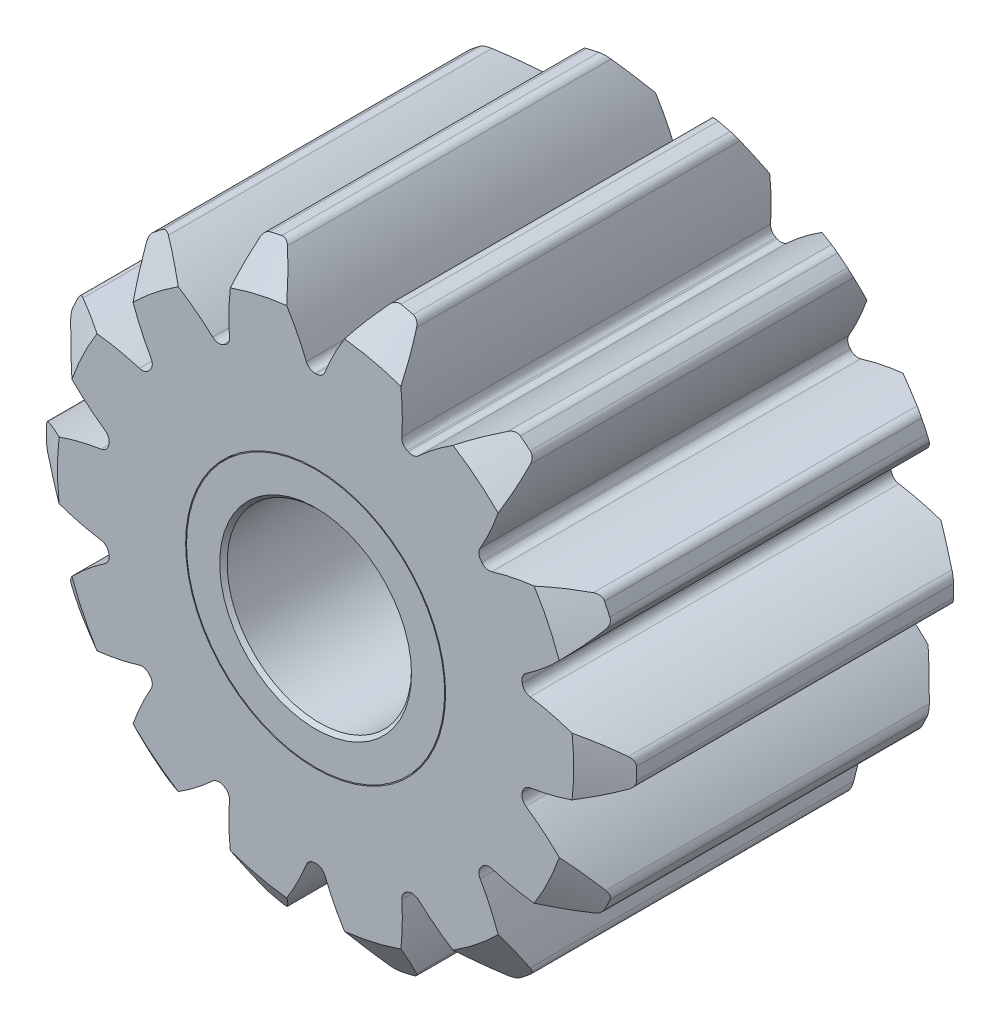
SolidWorks part; units mm, degrees
ref_plane "前视基准面" through (0, 0, 0) normal (0, 0, 1) x (1, 0, 0)
ref_plane "上视基准面" through (0, 0, 0) normal (0, 1, 0) x (1, 0, 0)
ref_plane "右视基准面" through (0, 0, 0) normal (1, 0, 0) x (0, 0, -1)
sketch "草图1" plane through (0, 0, 0) normal (1, 0, 0) x (0, 0, -1)
  line L0 (0, 0) -> (20, 0) construction
  line L1 (0, 5) -> (20, 5)
  line L4 (20, 5) -> (20, 16)
  line L5 (20, 16) -> (0, 16)
  line L6 (0, 16) -> (0, 5)
  line L7 (0, 0) -> (-2, 0) construction
  line L8 (-2, 0) -> (-2, -14) construction
  dimension "P" = 10
  dimension "B" = 20
  dimension "M" = 2
  dimension "Z" = 14
  dimension "D" = 32
sketch "草图2" plane through (0, 0, 0) normal (0, 0, 1) x (1, 0, 0)
  line L0 (0, 5) -> (0, 9) construction
  circle A0 centre (0, 0) radius 5
  circle A3 centre (0, 0) radius 7
  point P6 (0, 7)
  dimension "(D1)" = 4
sketch "草图11" plane through (-11.8785, -4, 0) normal (0, 0, 1) x (1, 0, 0)
  line L0 (11.8785, 4) -> (27.8785, 4) construction
  line L1 (25.7905, 2.4325) -> (11.8785, 4) construction
  circle A0 centre (11.8785, 4) radius 11.5
  arc A1 (23.1689, 1.8143) -> (23.3785, 4) centre (11.8785, 4) ccw construction
  arc A2 (25.7905, 2.4325) -> (25.8785, 4) centre (11.8785, 4) ccw construction
  arc A3 (27.8662, 3.3718) -> (27.8662, 4.6282) centre (11.8785, 4) ccw construction
  arc A4 (23.1689, 1.8143) -> (27.8662, 3.3718) centre (21.5405, 14.5867) ccw construction
  point P1 (25.8785, 4)
  point P7 (11.8785, 6)
  point P13 (25.7905, 2.4325)
  point P17 (27.8662, 4.6282)
  point P18 (23.1689, 6.1857)
  dimension "D1" = 32
  dimension "D" = 28
  dimension "D2" = 23
  dimension "m" = 2
  dimension "z" = 14
  dimension "D3" = 6.429
  dimension "D4" = 1.2566
  dimension "D5" = 4.3982
extrude "拉伸-齿轮a" add sketch "草图11" against normal blind 20
sketch "草图3" plane through (-1.3611, -4, 0) normal (0, 0, 1) x (1, 0, 0)
  line L1 (1.3611, 4) -> (17.3611, 4) construction
  line L2 (12.8611, 4) -> (17.3611, 4) construction
  circle A2 centre (1.3611, 4) radius 11.5 construction
  arc A3 (12.6514, 1.8143) -> (17.3487, 3.3718) centre (11.0231, 14.5867) ccw construction
  arc A4 (17.3487, 3.3718) -> (17.3487, 4.6282) centre (1.3611, 4) ccw construction
  arc A5 (12.6514, 1.8143) -> (12.6514, 6.1857) centre (1.3611, 4) ccw
  arc A6 (12.6514, 1.8143) -> (17.3487, 3.3718) centre (11.0231, 14.5867) ccw
  arc A7 (17.3487, 3.3718) -> (17.3487, 4.6282) centre (1.3611, 4) ccw
  arc A8 (12.6514, 6.1857) -> (17.3487, 4.6282) centre (11.0231, -6.5867) cw
extrude "拉伸-齿轮b" add sketch "草图3" along normal up to surface (-20 mm away) up to face at (11.5, 0, -20)
fillet "圆角-齿轮" radius 0.5 4 edges at (15.9877, -0.6282, -10) (15.9877, 0.6282, -10) (11.2904, -2.1857, -10) (11.2904, 2.1857, -10)
pattern_circular "阵列-齿轮" count 14 over 360 about axis through (0, 0, -20) along (0, 0, 1) of "拉伸-齿轮b", "圆角-齿轮"
sketch "草图4" plane through (0, 0, -20) normal (0, 0, -1) x (-1, 0, 0)
  line L0 (-14, 0) -> (-18, 0) construction
  circle A0 centre (0, 0) radius 18
  circle A1 centre (0, 0) radius 14
extrude "切除-齿轮" cut sketch "草图4" against normal blind 2 draft 55
extrude "切除-拉伸2" cut sketch "草图4<2>" along normal blind 2 draft 55 from vertex starting at point (0, 5, 0)
sketch "草图4<2>" plane through (0, 0, -20) normal (0, 0, -1) x (-1, 0, 0) same geometry as "草图4"
sketch "草图13" plane through (0, 0, 0) normal (0, 0, 1) x (1, 0, 0)
  circle A0 centre (0, 0) radius 5
extrude "切除-拉伸4" cut sketch "草图13" against normal through all
chamfer "倒角1" distance 0.2 angle 45 2 edges at (5, 0, -20) (5, 0, 0)
sketch "草图14" plane through (0, 0, 0) normal (1, 0, 0) x (0, 0, -1)
  line L0 (0, 0) -> (20, 0) construction
  line L1 (0, 7) -> (0, -7) construction
  line L2 (25, 7.05) -> (15, 7.05)
  line L3 (25, 7.05) -> (25, 7)
  line L4 (25, 7) -> (15, 7)
  line L5 (15, 7.05) -> (15, 7)
  line L6 (5, 7.05) -> (-5, 7.05)
  line L7 (5, 7.05) -> (5, 7)
  line L8 (5, 7) -> (-5, 7)
  line L9 (-5, 7.05) -> (-5, 7)
  line L10 (20, 5) -> (20, 16) construction
  line L11 (15, 7) -> (5, 7) construction
  point P12 (0, 7)
  point P16 (20, 7)
  dimension "D1" = 0.05
revolve "金属" cut sketch "草图14" angle 360 mid plane about L0
